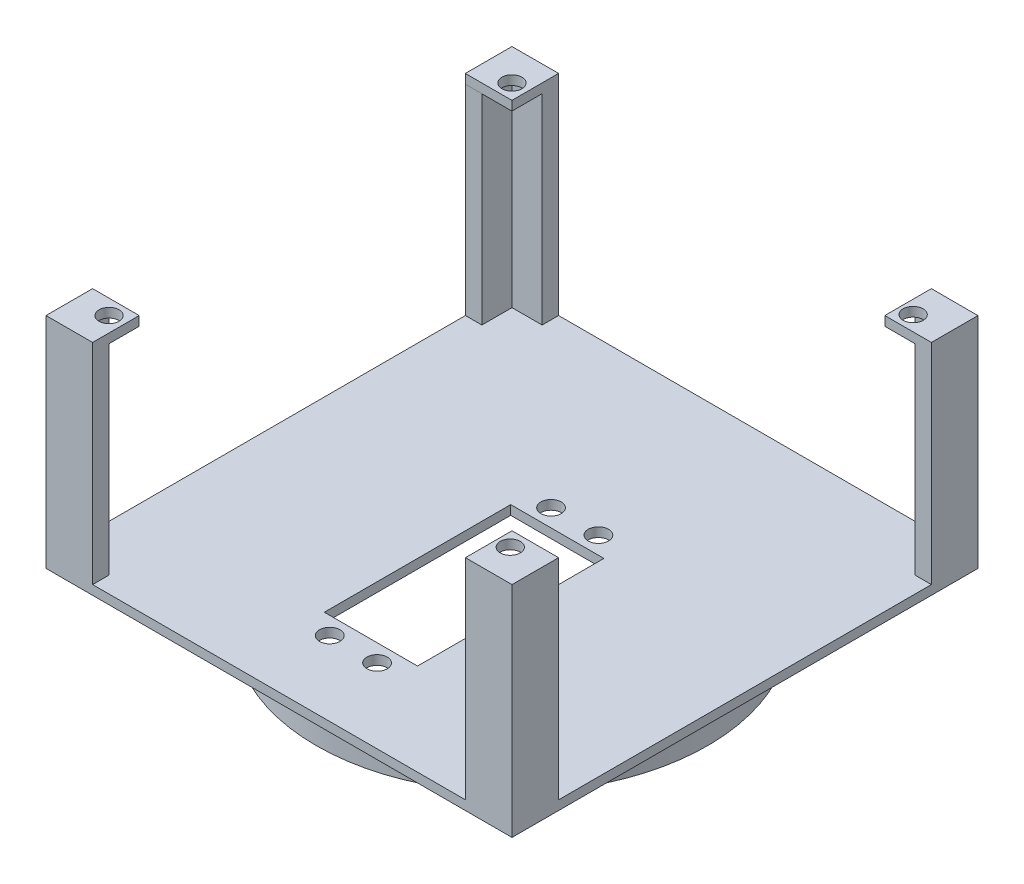
SolidWorks part; units mm, degrees
material "1060 Alloy"
ref_plane "Front Plane" through (0, 0, 0) normal (0, 0, 1) x (1, 0, 0)
ref_plane "Top Plane" through (0, 0, 0) normal (0, 1, 0) x (1, 0, 0)
ref_plane "Right Plane" through (0, 0, 0) normal (1, 0, 0) x (0, 0, -1)
sketch "Sketch1" plane through (0, 0, 0) normal (0, 1, 0) x (1, 0, 0)
  line L0 (0, -10.2787) -> (10, -10.2787)
  line L1 (10, -10.2787) -> (10, -50.2787)
  line L2 (0, -10.2787) -> (-10, -10.2787)
  line L3 (-10, -10.2787) -> (-10, -50.2787)
  line L4 (-10, -50.2787) -> (10, -50.2787)
  line L5 (0, -56.703) -> (0, -3.871) construction
  line L6 (-9.906, -30.287) -> (9.906, -30.287) construction
  line L7 (0, -3.871) -> (0, -10.2787) construction
  line L8 (-9.906, -20) -> (9.906, -20) construction
  line L9 (14.7387, -10.2787) -> (-14.7387, -10.2787) construction
  line L10 (-50, -70) -> (-46.4645, -66.4645)
  line L11 (-50, -70) -> (50, -70)
  line L12 (-50, -70) -> (-50, 30)
  line L13 (-50, 30) -> (50, 30)
  line L14 (50, -70) -> (50, 30)
  line L15 (-50, -70) -> (50, 30) construction
  line L16 (-50, 30) -> (50, -70) construction
  line L17 (-50, -70) -> (-40, -70)
  line L18 (-40, -70) -> (-40, -66.4645)
  line L19 (-40, -66.4645) -> (-46.4645, -66.4645)
  line L20 (-50, -70) -> (-50, -60)
  line L21 (-50, -60) -> (-46.4645, -60)
  line L22 (-46.4645, -60) -> (-46.4645, -66.4645)
  line L23 (-50, 30) -> (-50, 20)
  line L24 (-50, 20) -> (-46.4645, 20)
  line L25 (-46.4645, 20) -> (-46.4645, 26.4645)
  line L26 (-46.4645, 26.4645) -> (-40, 26.4645)
  line L27 (-40, 26.4645) -> (-40, 30)
  line L30 (50, 30) -> (50, 20)
  line L31 (50, 20) -> (46.4645, 20)
  line L32 (46.4645, 20) -> (46.4645, 26.4645)
  line L33 (46.4645, 26.4645) -> (40, 26.4645)
  line L34 (40, 26.4645) -> (40, 30)
  line L37 (46.4645, -60) -> (46.4645, -66.4645)
  line L38 (50, -60) -> (46.4645, -60)
  line L39 (50, -70) -> (50, -60)
  line L40 (40, -66.4645) -> (46.4645, -66.4645)
  line L41 (40, -70) -> (40, -66.4645)
  line L42 (50, -70) -> (40, -70)
  line L43 (50, -70) -> (46.4645, -66.4645)
  circle A0 centre (-5.08, -54.036) radius 2.1844
  arc A1 (-6.5248, -55.6743) -> (-3.6352, -55.6743) centre (-5.08, -54.036) cw
  circle A2 centre (5.08, -54.036) radius 2.1844
  circle A3 centre (0, -20) radius 40
  circle A4 centre (5.08, -6.538) radius 2.1844
  circle A5 centre (-5.08, -6.538) radius 2.1844
  circle A6 centre (0, -20) radius 42
  point P8 (0, -30.287)
  point P25 (0, -10.2787)
extrude "Boss-Extrude1" add sketch "Sketch1" along normal blind 2 contours L11 L41 L40 L37 L38 L14 L32 L13 L12 L21 L22 L19 L18 A5 A4 A2 A0 L4 L3 L2 L0 L1 | A3 A5 A4 L4 L3 L2 L0 L1 A0 A2 | A6 A3 region at (-45.0503, 0, 63.2322) region at (-38.8686, 0, 20) region at (-40.8121, 0, 20)
extrude "Boss-Extrude2" add sketch "Sketch1<3>" along normal blind 45 contours L34 L33 L32 L31 L14 L13 | L18 L19 L10 L11 | L22 L21 L12 L10 | L11 L43 L40 L41 | L43 L14 L38 L37 | L26 L27 L13 L12 L24 L25 region at (-48.3588, 0, 64.1794) region at (-44.1794, 0, 68.3588) region at (44.1794, 0, 68.3588) region at (-49.8586, 0, -25) region at (48.3588, 0, 64.1794) region at (48.2322, 0, -20.1414)
sketch "Sketch1<3>" plane through (0, 0, 0) normal (0, 1, 0) x (1, 0, 0) same geometry as "Sketch1"
sketch "Sketch2" plane through (0, 45, 0) normal (0, 1, 0) x (1, 0, 0)
  line L0 (50, -70) -> (50, -60)
  line L1 (50, -70) -> (40, -70)
  line L2 (40, -70) -> (40, -60)
  line L3 (40, -60) -> (50, -60)
  line L4 (-50, -70) -> (-40, -70)
  line L5 (-50, -70) -> (-50, -60)
  line L6 (-40, -70) -> (-40, -60)
  line L7 (-40, -60) -> (-50, -60)
  line L8 (-50, 29.9834) -> (-50, 19.9834)
  line L9 (-50, 29.9834) -> (-40, 30)
  line L10 (-40, 30) -> (-40, 19.9834)
  line L11 (-40, 19.9834) -> (-50, 19.9834)
  line L12 (50, 29.9834) -> (40, 30)
  line L13 (50, 29.9834) -> (50, 20)
  line L14 (50, 20) -> (40, 20)
  line L15 (40, 20) -> (40, 30)
  line L16 (46.4645, -60) -> (40, -60) construction
  line L17 (40, -60) -> (40, -66.4645) construction
  line L18 (-40, -60) -> (-46.4645, -60) construction
  line L20 (-46.4645, 19.9834) -> (-40, 19.9834) construction
  line L22 (-40, 23.2156) -> (-46.4645, 23.2156) construction
  line L23 (-46.4645, -60) -> (-40, -60) construction
  line L24 (-43.2322, -60) -> (-43.2322, -66.4645) construction
  line L25 (46.4645, -60) -> (40, -60) construction
  line L26 (42.8622, -60) -> (42.8622, -66.4645) construction
  line L27 (46.4645, 19.9834) -> (40, 20) construction
  line L28 (42.8622, 19.9834) -> (42.8622, 26.4479) construction
  circle A0 centre (42.8622, 23.2156) radius 2.15
  circle A1 centre (42.8622, -63.2322) radius 2.15
  circle A2 centre (-43.2322, -63.2322) radius 2.15
  circle A3 centre (-43.2322, 23.2156) radius 2.15
extrude "Boss-Extrude3" add sketch "Sketch2" along normal blind 2
extrude "Boss-Extrude4" add sketch "Sketch1<4>" against normal blind 11.9409 separate body contours A6 A3 region at (-40.8121, 0, 20)
sketch "Sketch1<4>" plane through (0, 0, 0) normal (0, 1, 0) x (1, 0, 0) same geometry as "Sketch1"
